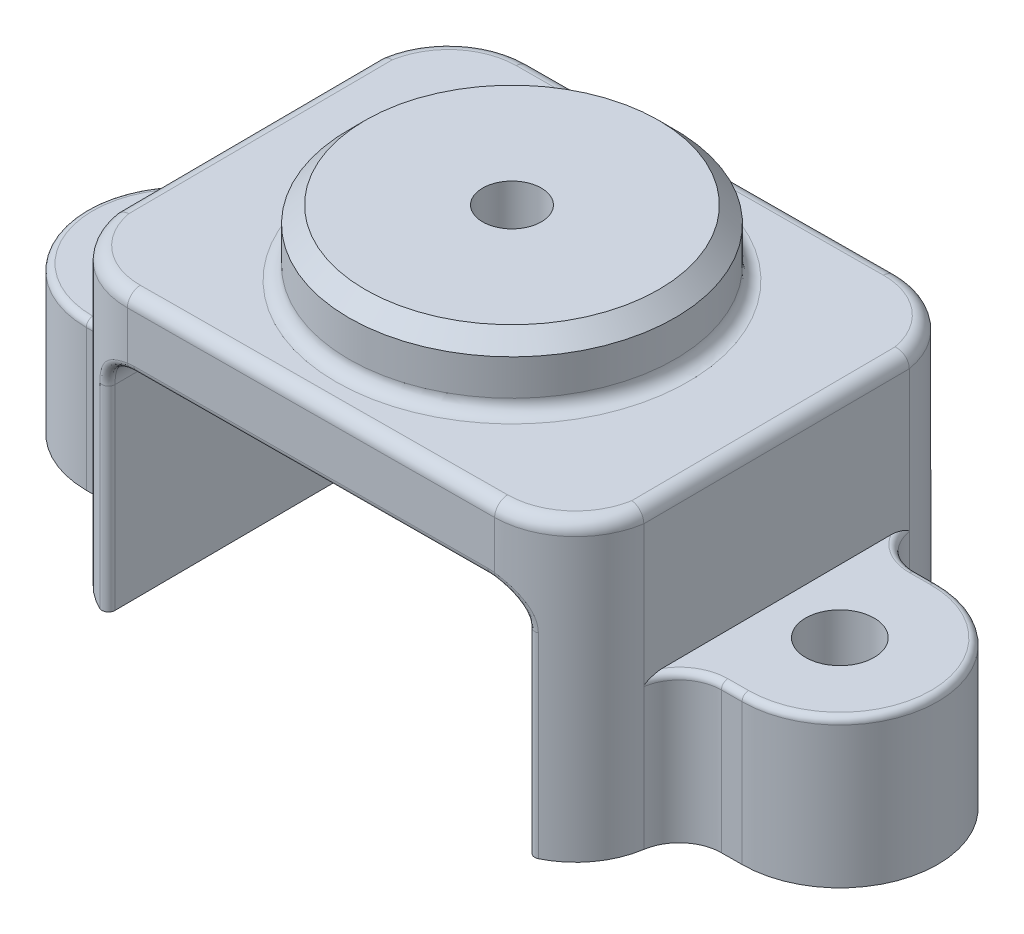
SolidWorks part; units mm, degrees
ref_plane "Front Plane" through (0, 0, 0) normal (0, 0, 1) x (1, 0, 0)
ref_plane "Top Plane" through (0, 0, 0) normal (0, 1, 0) x (1, 0, 0)
ref_plane "Right Plane" through (0, 0, 0) normal (1, 0, 0) x (0, 0, -1)
sketch "Sketch1" plane through (0, 0, 0) normal (0, 1, 0) x (1, 0, 0)
  line L0 (-5.5643, -6.2321) -> (5.6356, -6.1677)
  line L1 (-9.9998, -0.0575) -> (9.9998, 0.0575) construction
  line L2 (-5.6356, 6.1677) -> (5.5643, 6.2321)
  line L3 (-9.9998, -3.0575) -> (-9.3349, -3.0537)
  line L4 (9.3694, -2.9462) -> (9.9998, -2.9425)
  line L5 (-10.0343, 2.9423) -> (-9.3694, 2.9462)
  line L6 (9.3349, 3.0537) -> (9.9653, 3.0573)
  circle A0 centre (-9.9998, -0.0575) radius 1.05
  circle A1 centre (9.9998, 0.0575) radius 1.05
  arc A2 (-10.0003, 2.9425) -> (-9.9658, -3.0573) centre (-9.9998, -0.0575) ccw
  arc A3 (9.9998, -2.9425) -> (9.9653, 3.0573) centre (9.9998, 0.0575) ccw
  arc A4 (9.3694, -2.9462) -> (8.092, -4.0483) centre (9.3769, -4.2462) ccw
  arc A5 (5.6356, -6.1677) -> (8.092, -4.0483) centre (5.6212, -3.6677) ccw
  arc A6 (-8.045, -4.1411) -> (-5.5643, -6.2321) centre (-5.5786, -3.7321) ccw
  arc A7 (-8.045, -4.1411) -> (-9.3349, -3.0537) centre (-9.3275, -4.3537) ccw
  arc A8 (9.3349, 3.0537) -> (8.045, 4.1411) centre (9.3275, 4.3537) cw
  arc A9 (5.5643, 6.2321) -> (8.045, 4.1411) centre (5.5786, 3.7321) cw
  arc A10 (-8.092, 4.0483) -> (-5.6356, 6.1677) centre (-5.6212, 3.6677) cw
  arc A11 (-8.092, 4.0483) -> (-9.3694, 2.9462) centre (-9.3769, 4.2462) cw
  circle A12 centre (0, 0) radius 0.9
  dimension "D1" = 2.1
  dimension "D2" = 2.1
  dimension "D3" = 1.8
extrude "Boss-Extrude1" add sketch "Sketch1" along normal blind 9.05 contours A10 A11 L5 A2 L3 A7 A6 L0 A5 A4 L4 A3 L6 A8 A9 L2 A0 A12 A1 region at (-7.0041, 0, 5.4232)
sketch "Sketch2" plane through (0.0356, 0, 6.1999) normal (0.0057, 0, 1) x (1, 0, -0.0057)
  line L0 (-5.6, 0) -> (5.6, 0) construction
  line L1 (-5.4, 7) -> (5.4, 7)
  line L2 (-6.4, 6) -> (-6.4, 0)
  line L3 (-6.4, 0) -> (6.4, 0)
  line L4 (6.4, 6) -> (6.4, 0)
  line L5 (-6.4, 7) -> (6.4, 0) construction
  line L6 (-6.4, 0) -> (6.4, 7) construction
  line L15 (-8.0686, 9.05) -> (-8.0686, 4.525)
  line L16 (-8.0686, 9.05) -> (-8.0686, 0) construction
  line L20 (-8.0686, 4.525) -> (-13, 4.525)
  line L22 (-13, 9.05) -> (-13, 0) construction
  line L23 (-13, 4.525) -> (-13, 9.05)
  line L24 (-10.0172, 9.05) -> (-13, 9.05) construction
  line L25 (-13, 9.05) -> (-8.0686, 9.05)
  line L26 (8.0686, 9.05) -> (8.0686, 0) construction
  line L27 (13, 9.05) -> (8.0686, 9.05)
  line L28 (13, 9.05) -> (13, 4.525)
  line L29 (13, 4.525) -> (8.0686, 4.525)
  line L30 (8.0686, 9.05) -> (8.0686, 4.525)
  arc A0 (5.4, 7) -> (6.4, 6) centre (5.4, 6) cw
  arc A1 (-5.4, 7) -> (-6.4, 6) centre (-5.4, 6) ccw
  point P0 (0, 3.5)
  point P5 (0, 7)
  dimension "D3" = 1
  dimension "D1" = 12.8
  dimension "D2" = 7
extrude "Cut-Extrude1" cut sketch "Sketch2" against normal through all
sketch "Sketch3" plane through (0, 9.05, 0) normal (0, 1, 0) x (1, 0, 0)
  circle A0 centre (0, 0) radius 0.9
  circle A1 centre (0, 0) radius 5
  dimension "D1" = 10
extrude "Boss-Extrude2" add sketch "Sketch3" along normal blind 2
fillet "Fillet1" radius 0.2 24 edges at (8.4896, 4.525, -3.3597) (9.6501, 4.525, -3.0555) (8.5277, 4.525, 3.2619) (9.6846, 4.525, 2.9443) (-8.5277, 4.525, -3.2619) (-8.4896, 4.525, 3.3597) (-9.6674, 4.525, 3.0556) (6.365, 3, -6.1052) (6.1179, 6.6577, -6.1733) (5.4648, 6.9949, -6.2315) (-0.0356, 7, -6.1999) (-5.5361, 6.9949, -6.1683) (-6.2295, 6.6074, -6.0926) (-6.365, 3, 6.1052) (-6.159, 6.6074, 6.1638) (-5.4648, 6.9949, 6.2315) (0.0356, 7, 6.1999) (5.5361, 6.9949, 6.1683) (6.1885, 6.6577, 6.1025) (12.9998, 4.525, -0.0747) (-12.9998, 4.525, 0.0747) (-9.7019, 4.525, -2.9442) (-6.4348, 3, -6.0316) (6.4348, 3, 6.0316)
fillet "Fillet2" radius 0.4 9 edges at (7.2543, 9.05, 5.5606) (0.0356, 9.05, 6.1999) (-7.1899, 9.05, 5.6436) (-8.0685, 9.05, 0.0464) (-7.2543, 9.05, -5.5606) (-0.0356, 9.05, -6.1999) (7.1899, 9.05, -5.6436) (8.0685, 9.05, -0.0464) (0, 9.05, 5)
chamfer "Chamfer1" distance 0.5 angle 45 1 edges at (0, 11.05, 5)
